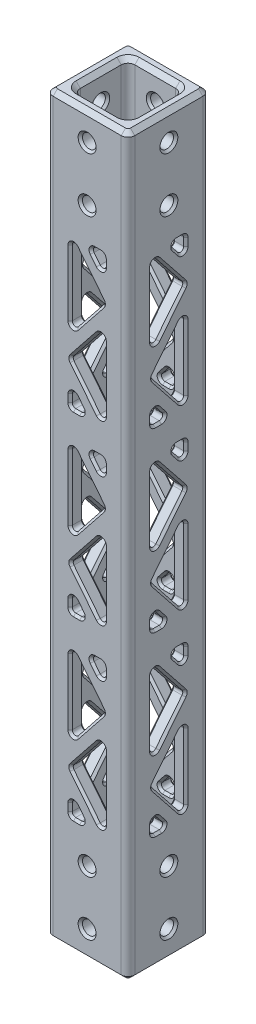
SolidWorks part; units mm, degrees
note: '?' marks a value the reader was unsure of.
ref_plane "Front Plane" through (0, 0, 0) normal (0, 0, 1) x (1, 0, 0)
ref_plane "Top Plane" through (0, 0, 0) normal (0, 1, 0) x (1, 0, 0)
ref_plane "Right Plane" through (0, 0, 0) normal (1, 0, 0) x (0, 0, -1)
sketch "Sketch1" plane through (0, 0, 0) normal (0, 1, 0) x (1, 0, 0)
  line L1 (-9.525, -9.525) -> (9.525, -9.525)
  line L2 (-9.525, -9.525) -> (-9.525, 9.525)
  line L3 (-9.525, 9.525) -> (9.525, 9.525)
  line L4 (9.525, -9.525) -> (9.525, 9.525)
  line L5 (-9.525, -9.525) -> (9.525, 9.525) construction
  line L6 (-9.525, 9.525) -> (9.525, -9.525) construction
  line L7 (-6.35, -6.35) -> (6.35, -6.35)
  line L8 (-6.35, -6.35) -> (-6.35, 6.35)
  line L9 (-6.35, 6.35) -> (6.35, 6.35)
  line L10 (6.35, -6.35) -> (6.35, 6.35)
  line L11 (-6.35, -6.35) -> (6.35, 6.35) construction
  line L12 (-6.35, 6.35) -> (6.35, -6.35) construction
  point P0 (0, 0)
  point P6 (0, 0)
  dimension "D1" = 19.05
  dimension "D2" = 19.05
  dimension "D3" = 12.7
extrude "Boss-Extrude1" add sketch "Sketch1" along normal mid plane 171.45 contours L3 L4 L1 L2
hole_wizard "1/8 (0.125) Diameter Hole1" positions "Sketch8" profile "Sketch9" hole size "1/8" standard "ANSI Inch" end condition through all
sketch "Sketch8" plane through (-9.525, 0, 0) normal (-1, 0, 0) x (0, 0, 1)
  line L4 (-9.525, 85.725) -> (9.525, 85.725) construction
  line L5 (0, 79.375) -> (0, 85.725) construction
  point P0 (0, 79.375)
  point P2 (0, 66.675)
  dimension "D1" = 12.7
  dimension "D2" = 6.35
sketch "Sketch9" plane through (-9.525, 79.375, 0) normal (0, 1, 0) x (0, 0, 1)
  line L0 (0, 0) -> (0, 19.05)
  line L1 (0, 19.05) -> (1.5875, 19.05)
  line L2 (1.5875, 19.05) -> (1.5875, 0)
  line L5 (1.5875, 0) -> (0, 0)
  line L11 (0, -6.35) -> (0, 107.95) construction
  dimension "Thru Hole Dia." = 3.175
  dimension "Thru Hole Depth" = 19.05
hole_wizard "1/8 (0.125) Diameter Hole2" positions "Sketch10" profile "Sketch11" hole size "1/8" standard "ANSI Inch" end condition through all
sketch "Sketch10" plane through (-9.525, 0, 0) normal (-1, 0, 0) x (0, 0, 1)
  line L0 (0, -85.725) -> (0, -79.375) construction
  line L1 (-9.525, -85.725) -> (9.525, -85.725) construction
  point P0 (0, -66.675)
  point P2 (0, -79.375)
  dimension "D1" = 12.7
  dimension "D2" = 6.35
sketch "Sketch11" plane through (-9.525, -66.675, 0) normal (0, 1, 0) x (0, 0, 1)
  line L0 (0, 0) -> (0, 19.05)
  line L1 (0, 19.05) -> (1.5875, 19.05)
  line L2 (1.5875, 19.05) -> (1.5875, 0)
  line L5 (1.5875, 0) -> (0, 0)
  line L11 (0, -6.35) -> (0, 107.95) construction
  dimension "Thru Hole Dia." = 3.175
  dimension "Thru Hole Depth" = 19.05
hole_wizard "1/8 (0.125) Diameter Hole3" positions "Sketch15" profile "Sketch16" hole size "1/8" standard "ANSI Inch" end condition through all
sketch "Sketch15" plane through (0, 0, 9.525) normal (0, 0, 1) x (1, 0, 0)
  line L0 (0, -85.725) -> (0, -79.375) construction
  line L1 (-9.525, -85.725) -> (9.525, -85.725) construction
  line L2 (0, -79.375) -> (0, -66.675) construction
  line L4 (0, 66.675) -> (0, 79.375) construction
  line L5 (0, 79.375) -> (0, 85.725) construction
  line L6 (-9.525, 85.725) -> (9.525, 85.725) construction
  point P0 (0, 79.375)
  point P2 (0, 66.675)
  point P4 (0, -66.675)
  point P6 (0, -79.375)
  dimension "D1" = 6.35
  dimension "D2" = 12.7
sketch "Sketch16" plane through (0, 79.375, 9.525) normal (1, 0, 0) x (0, -1, 0)
  line L0 (0, 0) -> (0, 19.05)
  line L1 (0, 19.05) -> (1.5875, 19.05)
  line L2 (1.5875, 19.05) -> (1.5875, 0)
  line L5 (1.5875, 0) -> (0, 0)
  line L11 (0, -6.35) -> (0, 107.95) construction
  dimension "Thru Hole Dia." = 3.175
  dimension "Thru Hole Depth" = 19.05
sketch "Sketch14" plane through (0, 0, 0) normal (1, 0, 0) x (0, 0, -1)
  line L0 (-3.9688, 58.7375) -> (3.9688, 58.7375) construction
  line L3 (3.9688, 58.7375) -> (3.9688, -58.7375) construction
  line L6 (3.9688, -58.7375) -> (-3.9688, -58.7375) construction
  line L9 (-3.9688, -58.7375) -> (-3.9688, 58.7375) construction
  line L10 (0, 58.7375) -> (0, 65.0875) construction
  line L11 (0, -65.0875) -> (0, -58.7375) construction
  line L12 (-3.9688, 23.8125) -> (3.9688, 23.8125) construction
  line L13 (-3.9688, 17.4625) -> (3.9688, 17.4625) construction
  line L14 (-3.9688, -17.4625) -> (3.9688, -17.4625) construction
  line L15 (-3.9688, -23.8125) -> (3.9688, -23.8125) construction
  line L16 (0, -58.7375) -> (0, -23.8125) construction
  line L17 (0, -23.8125) -> (0, -17.4625) construction
  line L18 (0, -17.4625) -> (0, 17.4625) construction
  line L19 (0, 17.4625) -> (0, 23.8125) construction
  line L20 (0, 23.8125) -> (0, 58.7375) construction
  line L21 (-3.9688, 58.7375) -> (-0.0935, 58.7375)
  line L22 (-0.0935, 58.7375) -> (-3.9688, 53.8821)
  line L23 (-3.9688, 53.8821) -> (-3.9688, 58.7375)
  line L24 (3.9688, 58.7375) -> (-3.9688, 48.7924)
  line L25 (-3.9688, 48.7924) -> (3.9688, 38.8473)
  line L26 (3.9688, 38.8473) -> (3.9688, 58.7375)
  line L27 (-3.9688, 23.8125) -> (3.9688, 33.7576)
  line L28 (3.9688, 33.7576) -> (-3.9688, 43.7027)
  line L29 (-3.9688, 43.7027) -> (-3.9688, 23.8125)
  line L30 (0, 53.765) -> (-2.4815, 55.7455) construction
  line L31 (0, 43.8199) -> (-2.4815, 41.8393) construction
  line L32 (0.0935, 23.8125) -> (3.9688, 23.8125)
  line L33 (3.9688, 23.8125) -> (3.9688, 28.6679)
  line L34 (3.9688, 28.6679) -> (0.0935, 23.8125)
  line L35 (0, 28.785) -> (2.4815, 26.8045) construction
  line L36 (-3.9688, 17.4625) -> (-0.0935, 17.4625)
  line L37 (-0.0935, 17.4625) -> (-3.9688, 12.6071)
  line L38 (-3.9688, 12.6071) -> (-3.9688, 17.4625)
  line L39 (3.9688, 17.4625) -> (-3.9688, 7.5174)
  line L40 (-3.9688, 7.5174) -> (3.9688, -2.4277)
  line L41 (3.9688, -2.4277) -> (3.9688, 17.4625)
  line L42 (0, 12.49) -> (-2.4815, 14.4705) construction
  line L43 (-3.9688, -17.4625) -> (3.9688, -7.5174)
  line L44 (3.9688, -7.5174) -> (-3.9688, 2.4277)
  line L45 (-3.9688, 2.4277) -> (-3.9688, -17.4625)
  line L46 (0, -2.5449) -> (2.4815, -0.5643) construction
  line L47 (0.0935, -17.4625) -> (3.9688, -17.4625)
  line L48 (3.9688, -17.4625) -> (3.9688, -12.6071)
  line L49 (3.9688, -12.6071) -> (0.0935, -17.4625)
  line L50 (2.0311, -15.0348) -> (-0.4504, -13.0542) construction
  line L51 (-3.9688, -23.8125) -> (-0.0935, -23.8125)
  line L52 (-0.0935, -23.8125) -> (-3.9688, -28.6679)
  line L53 (-3.9688, -28.6679) -> (-3.9688, -23.8125)
  line L54 (3.9688, -23.8125) -> (-3.9688, -33.7576)
  line L55 (-3.9688, -33.7576) -> (3.9688, -43.7027)
  line L56 (3.9688, -43.7027) -> (3.9688, -23.8125)
  line L57 (3.9688, -58.7375) -> (0.0935, -58.7375)
  line L58 (0.0935, -58.7375) -> (3.9688, -53.8821)
  line L59 (3.9688, -53.8821) -> (3.9688, -58.7375)
  line L60 (-3.9688, -58.7375) -> (3.9688, -48.7924)
  line L61 (3.9688, -48.7924) -> (-3.9688, -38.8473)
  line L62 (-3.9688, -38.8473) -> (-3.9688, -58.7375)
  line L63 (0, -28.785) -> (-2.4815, -26.8045) construction
  line L64 (0, -38.7301) -> (-2.4815, -40.7107) construction
  line L65 (2.0311, -56.3098) -> (-0.4504, -54.3292) construction
  circle A8 centre (0, 66.675) radius 1.5875 construction
  circle A9 centre (0, -66.675) radius 1.5875 construction
  dimension "D3" = 3.175
  dimension "D2" = 6.35
  dimension "D1" = 7.9375
extrude "Cut-Extrude1" cut sketch "Sketch14" against normal up to next
ref_axis "Axis1" through (0, -87.3125, 0) along (0, 1, 0)?
pattern_circular "CirPattern1" count 4 over 360 about axis through (0, 0, 0) along (0, 1, 0) of "Cut-Extrude1"
fillet "Fillet1" radius 1.5875 8 edges at (9.525, 0, -9.525) (9.525, 0, 9.525) (-9.525, 0, -9.525) (-9.525, 0, 9.525) (6.35, 0, -6.35) (6.35, 0, 6.35) (-6.35, 0, 6.35) (-6.35, 0, -6.35)
fillet "Fillet2" radius 0.7937 71 edges at (-3.9688, 7.5174, -7.9375) (3.9687, -2.4277, -7.9375) (0.0935, 23.8125, -7.9375) (3.9687, 23.8125, -7.9375) (3.9687, 33.7576, -7.9375) (-3.9688, 43.7027, -7.9375) (-0.0935, 17.4625, -7.9375) (-3.9688, -58.7375, -7.9375) (3.9687, -48.7924, -7.9375) (-3.9688, -38.8473, -7.9375) (3.9687, -12.6071, -7.9375) (3.9687, -53.8821, -7.9375) (0.0935, -58.7375, -7.9375) (3.9687, -58.7375, -7.9375) (3.9687, 38.8473, -7.9375) (-3.9688, 53.8821, -7.9375) (-3.9688, 58.7375, -7.9375) (7.9375, -23.8125, 3.9687) (7.9375, -43.7027, 3.9688) (7.9375, -23.8125, -0.0935) (7.9375, -23.8125, -3.9688) (7.9375, 17.4625, 3.9688) (7.9375, 7.5174, -3.9687) (7.9375, 23.8125, 0.0935) (7.9375, 23.8125, -3.9688) (7.9375, 12.6071, -3.9688) (7.9375, 17.4625, -0.0935) (7.9375, 17.4625, -3.9688) (7.9375, -58.7375, -3.9687) (7.9375, -48.7924, 3.9688) (7.9375, -38.8473, -3.9688) (7.9375, -12.6071, 3.9688) (7.9375, -53.8821, 3.9687) (7.9375, -58.7375, 0.0935) (7.9375, 58.7375, 3.9688) (7.9375, 48.7924, -3.9687) (7.9375, 53.8821, -3.9688) (7.9375, 58.7375, -0.0935) (-3.9687, -23.8125, 7.9375) (3.9688, -33.7576, 7.9375) (3.9688, -28.6679, 7.9375) (0.0935, -23.8125, 7.9375) (3.9688, 2.4277, 7.9375) (-3.9687, 17.4625, 7.9375) (3.9688, 7.5174, 7.9375) (-3.9687, -2.4277, 7.9375) (-3.9687, 28.6679, 7.9375) (-3.9687, 33.7576, 7.9375) (3.9688, -38.8473, 7.9375) (-3.9687, -17.4625, 7.9375) (-3.9687, -12.6071, 7.9375) (-0.0935, -58.7375, 7.9375) (0.0935, 58.7375, 7.9375) (-7.9375, -53.8821, -3.9688) (-7.9375, -58.7375, 3.9687) (-7.9375, -33.7576, 3.9688) (-7.9375, -28.6679, 3.9688) (-7.9375, -23.8125, 0.0935) (-7.9375, -12.6071, -3.9688) (-7.9375, 7.5174, 3.9688) (-7.9375, -2.4277, -3.9688) (-7.9375, 17.4625, 0.0935) (-7.9375, 17.4625, 3.9688) (-7.9375, 23.8125, -0.0935) (-7.9375, 28.6679, -3.9688) (-7.9375, 33.7576, -3.9688) (-7.9375, 43.7027, 3.9688) (-7.9375, 48.7924, 3.9688) (-7.9375, 38.8473, -3.9688) (-7.9375, 58.7375, 0.0935) (-7.9375, 58.7375, 3.9688)
chamfer "Chamfer2" distance 1.016 angle 45 32 edges at (5.885, 85.725, -5.885) (0, 85.725, -6.35) (-5.885, 85.725, -5.885) (-6.35, 85.725, 0) (-5.885, 85.725, 5.885) (0, 85.725, 6.35) (5.885, 85.725, 5.885) (6.35, 85.725, 0) (9.06, 85.725, 9.06) (0, 85.725, 9.525) (-9.06, 85.725, 9.06) (-9.525, 85.725, 0) (-9.06, 85.725, -9.06) (0, 85.725, -9.525) (9.06, 85.725, -9.06) (9.525, 85.725, 0) (-5.885, -85.725, -5.885) (0, -85.725, -6.35) (5.885, -85.725, -5.885) (6.35, -85.725, 0) (5.885, -85.725, 5.885) (0, -85.725, 6.35) (-5.885, -85.725, 5.885) (-6.35, -85.725, 0) (-9.06, -85.725, -9.06) (-9.525, -85.725, 0) (-9.06, -85.725, 9.06) (0, -85.725, 9.525) (9.06, -85.725, 9.06) (9.525, -85.725, 0) (9.06, -85.725, -9.06) (0, -85.725, -9.525)
chamfer "Chamfer1" distance 0.508 angle 45 608 edges at (-3.4373, 25.3303, -6.35) (-3.4373, 25.3303, -9.525) (3.7469, 33.7576, -6.35) (3.7469, 33.7576, -9.525) (-3.4373, 42.1849, -6.35) (-3.4373, 42.1849, -9.525) (-3.4373, 14.1249, -6.35) (-3.4373, 14.1249, -9.525) (-1.0274, 17.013, -6.35) (-1.0274, 17.013, -9.525) (-3.7363, 17.23, -6.35) (-3.7363, 17.23, -9.525) (-3.4373, -57.2197, -6.35) (-3.4373, -57.2197, -9.525) (3.7469, -48.7924, -6.35) (3.7469, -48.7924, -9.525) (-3.4373, -40.3651, -6.35) (-3.4373, -40.3651, -9.525) (1.0274, -17.013, -6.35) (1.0274, -17.013, -9.525) (3.7363, -17.23, -6.35) (3.7363, -17.23, -9.525) (3.4373, -14.1249, -6.35) (3.4373, -14.1249, -9.525) (3.4373, -55.3999, -6.35) (3.4373, -55.3999, -9.525) (1.0274, -58.288, -6.35) (1.0274, -58.288, -9.525) (3.7363, -58.505, -6.35) (3.7363, -58.505, -9.525) (3.4373, 57.2197, -6.35) (3.4373, 57.2197, -9.525) (-3.7469, 48.7924, -6.35) (-3.7469, 48.7924, -9.525) (3.4373, 40.3651, -6.35) (3.4373, 40.3651, -9.525) (-3.4373, 55.3999, -6.35) (-3.4373, 55.3999, -9.525) (-1.0274, 58.288, -6.35) (-1.0274, 58.288, -9.525) (-3.7363, 58.505, -6.35) (-3.7363, 58.505, -9.525) (6.35, -25.3303, 3.4373) (9.525, -25.3303, 3.4373) (6.35, -33.7576, -3.7469) (9.525, -33.7576, -3.7469) (6.35, -42.1849, 3.4373) (9.525, -42.1849, 3.4373) (6.35, -27.1501, -3.4373) (9.525, -27.1501, -3.4373) (6.35, -24.262, -1.0274) (9.525, -24.262, -1.0274) (6.35, -24.045, -3.7363) (9.525, -24.045, -3.7363) (6.35, -15.9447, -3.4373) (9.525, -15.9447, -3.4373) (6.35, -7.5174, 3.7469) (9.525, -7.5174, 3.7469) (6.35, 0.9099, -3.4373) (9.525, 0.9099, -3.4373) (6.35, 15.9447, 3.4373) (9.525, 15.9447, 3.4373) (6.35, 7.5174, -3.7469) (9.525, 7.5174, -3.7469) (6.35, -0.9099, 3.4373) (9.525, -0.9099, 3.4373) (6.35, 27.1501, 3.4373) (9.525, 27.1501, 3.4373) (6.35, 24.262, 1.0274) (9.525, 24.262, 1.0274) (6.35, 24.045, 3.7363) (9.525, 24.045, 3.7363) (6.35, 25.3303, -3.4373) (9.525, 25.3303, -3.4373) (6.35, 33.7576, 3.7469) (9.525, 33.7576, 3.7469) (6.35, 42.1849, -3.4373) (9.525, 42.1849, -3.4373) (6.35, 14.1249, -3.4373) (9.525, 14.1249, -3.4373) (6.35, 17.013, -1.0274) (9.525, 17.013, -1.0274) (6.35, 17.23, -3.7363) (9.525, 17.23, -3.7363) (6.35, -57.2197, -3.4373) (9.525, -57.2197, -3.4373) (6.35, -48.7924, 3.7469) (9.525, -48.7924, 3.7469) (6.35, -40.3651, -3.4373) (9.525, -40.3651, -3.4373) (6.35, -17.013, 1.0274) (9.525, -17.013, 1.0274) (6.35, -17.23, 3.7363) (9.525, -17.23, 3.7363) (6.35, -14.1249, 3.4373) (9.525, -14.1249, 3.4373) (6.35, -55.3999, 3.4373) (9.525, -55.3999, 3.4373) (6.35, -58.288, 1.0274) (9.525, -58.288, 1.0274) (6.35, -58.505, 3.7363) (9.525, -58.505, 3.7363) (6.35, 57.2197, 3.4373) (9.525, 57.2197, 3.4373) (6.35, 48.7924, -3.7469) (9.525, 48.7924, -3.7469) (6.35, 40.3651, 3.4373) (9.525, 40.3651, 3.4373) (6.35, 55.3999, -3.4373) (9.525, 55.3999, -3.4373) (6.35, 58.288, -1.0274) (9.525, 58.288, -1.0274) (-3.4373, -25.3303, 6.35) (-3.4373, -25.3303, 9.525) (3.7469, -33.7576, 6.35) (3.7469, -33.7576, 9.525) (-3.4373, -42.1849, 6.35) (-3.4373, -42.1849, 9.525) (3.4373, -27.1501, 6.35) (3.4373, -27.1501, 9.525) (1.0274, -24.262, 6.35) (1.0274, -24.262, 9.525) (3.7363, -24.045, 6.35) (3.7363, -24.045, 9.525) (3.4373, -15.9447, 6.35) (3.4373, -15.9447, 9.525) (-3.7469, -7.5174, 6.35) (-3.7469, -7.5174, 9.525) (3.4373, 0.9099, 6.35) (3.4373, 0.9099, 9.525) (-3.4373, 15.9447, 6.35) (-3.4373, 15.9447, 9.525) (3.7469, 7.5174, 6.35) (3.7469, 7.5174, 9.525) (-3.4373, -0.9099, 6.35) (-3.4373, -0.9099, 9.525) (-3.4373, 27.1501, 6.35) (-3.4373, 27.1501, 9.525) (-1.0274, 24.262, 6.35) (-1.0274, 24.262, 9.525) (-3.7363, 24.045, 6.35) (-3.7363, 24.045, 9.525) (3.4373, 25.3303, 6.35) (3.4373, 25.3303, 9.525) (-3.7469, 33.7576, 6.35) (-3.7469, 33.7576, 9.525) (3.4373, 42.1849, 6.35) (3.4373, 42.1849, 9.525) (3.4373, 14.1249, 6.35) (3.4373, 14.1249, 9.525) (1.0274, 17.013, 6.35) (1.0274, 17.013, 9.525) (3.7363, 17.23, 6.35) (3.7363, 17.23, 9.525) (3.4373, -57.2197, 6.35) (3.4373, -57.2197, 9.525) (-3.7469, -48.7924, 6.35) (-3.7469, -48.7924, 9.525) (3.4373, -40.3651, 6.35) (3.4373, -40.3651, 9.525) (-1.0274, -17.013, 6.35) (-1.0274, -17.013, 9.525) (-3.7363, -17.23, 6.35) (-3.7363, -17.23, 9.525) (-3.4373, -14.1249, 6.35) (-3.4373, -14.1249, 9.525) (-3.4373, -55.3999, 6.35) (-3.4373, -55.3999, 9.525) (-1.0274, -58.288, 6.35) (-1.0274, -58.288, 9.525) (-3.7363, -58.505, 6.35) (-3.7363, -58.505, 9.525) (-3.4373, 57.2197, 6.35) (-3.4373, 57.2197, 9.525) (3.7469, 48.7924, 6.35) (3.7469, 48.7924, 9.525) (-3.4373, 40.3651, 6.35) (-3.4373, 40.3651, 9.525) (3.4373, 55.3999, 6.35) (3.4373, 55.3999, 9.525) (1.0274, 58.288, 6.35) (1.0274, 58.288, 9.525) (3.7363, 58.505, 6.35) (3.7363, 58.505, 9.525) (6.35, 58.505, -3.7363) (9.525, 58.505, -3.7363) (6.35, 66.675, 1.5875) (-6.35, 66.675, -1.5875) (-9.525, 66.675, 1.5875) (9.525, 66.675, 1.5875) (6.35, 79.375, 1.5875) (-6.35, 79.375, -1.5875) (-9.525, 79.375, 1.5875) (9.525, 79.375, 1.5875) (6.35, -79.375, 1.5875) (-6.35, -79.375, -1.5875) (-9.525, -79.375, 1.5875) (9.525, -79.375, 1.5875) (6.35, -66.675, 1.5875) (-6.35, -66.675, -1.5875) (-9.525, -66.675, 1.5875) (9.525, -66.675, 1.5875) (-9.525, -58.7375, -2.4588) (-6.35, -58.7375, -2.4588) (-9.525, -56.5513, -1.8384) (-6.35, -56.5513, -1.8384) (-9.525, -57.0464, -3.9688) (-6.35, -57.0464, -3.9688) (-9.525, -44.4582, -0.5095) (-6.35, -44.4582, -0.5095) (-9.525, -53.1266, -0.5095) (-6.35, -53.1266, -0.5095) (-9.525, -48.7924, 3.9688) (-6.35, -48.7924, 3.9688) (-9.525, -38.0918, 0.5095) (-6.35, -38.0918, 0.5095) (-9.525, -29.4234, 0.5095) (-6.35, -29.4234, 0.5095) (-9.525, -33.7576, -3.9688) (-6.35, -33.7576, -3.9688) (-9.525, -25.9987, 1.8384) (-6.35, -25.9987, 1.8384) (-9.525, -25.5036, 3.9688) (-6.35, -25.5036, 3.9688) (-9.525, -23.8125, 2.4588) (-6.35, -23.8125, 2.4588) (-9.525, -15.7714, -3.9688) (-6.35, -15.7714, -3.9688) (-9.525, -17.4625, -2.4588) (-6.35, -17.4625, -2.4588) (-9.525, -15.2763, -1.8384) (-6.35, -15.2763, -1.8384) (-9.525, -11.8516, -0.5095) (-6.35, -11.8516, -0.5095) (-9.525, -7.5174, 3.9688) (-6.35, -7.5174, 3.9688) (-9.525, -3.1832, -0.5095) (-6.35, -3.1832, -0.5095) (-9.525, 3.1832, 0.5095) (-6.35, 3.1832, 0.5095) (-9.525, 11.8516, 0.5095) (-6.35, 11.8516, 0.5095) (-9.525, 7.5174, -3.9688) (-6.35, 7.5174, -3.9688) (-9.525, 17.4625, 2.4588) (-6.35, 17.4625, 2.4588) (-9.525, 15.2763, 1.8384) (-6.35, 15.2763, 1.8384) (-9.525, 15.7714, 3.9688) (-6.35, 15.7714, 3.9688) (-9.525, 23.8125, -2.4588) (-6.35, 23.8125, -2.4588) (-9.525, 25.9987, -1.8384) (-6.35, 25.9987, -1.8384) (-9.525, 25.5036, -3.9688) (-6.35, 25.5036, -3.9688) (-9.525, 38.0918, -0.5095) (-6.35, 38.0918, -0.5095) (-9.525, 29.4234, -0.5095) (-6.35, 29.4234, -0.5095) (-9.525, 33.7576, 3.9688) (-6.35, 33.7576, 3.9688) (-1.5875, -79.375, 6.35) (-9.525, 44.4582, 0.5095) (1.5875, -79.375, -6.35) (-6.35, 44.4582, 0.5095) (1.5875, -79.375, -9.525) (-9.525, 53.1266, 0.5095) (1.5875, -79.375, 9.525) (-6.35, 53.1266, 0.5095) (-9.525, 48.7924, -3.9688) (-6.35, 48.7924, -3.9688) (-9.525, 58.7375, 2.4588) (-6.35, 58.7375, 2.4588) (-9.525, 56.5513, 1.8384) (-6.35, 56.5513, 1.8384) (-9.525, 57.0464, 3.9688) (-6.35, 57.0464, 3.9688) (-0.5095, -29.4234, -9.525) (-0.5095, -29.4234, -6.35) (3.9687, -33.7576, -9.525) (3.9687, -33.7576, -6.35) (-0.5095, -38.0918, -9.525) (-0.5095, -38.0918, -6.35) (-1.8384, -25.9987, -9.525) (-1.8384, -25.9987, -6.35) (-3.9688, -25.5036, -9.525) (-3.9688, -25.5036, -6.35) (-2.4588, -23.8125, -9.525) (-2.4588, -23.8125, -6.35) (0.5095, -11.8516, -9.525) (0.5095, -11.8516, -6.35) (-3.9688, -7.5174, -9.525) (-3.9688, -7.5174, -6.35) (0.5095, -3.1832, -9.525) (0.5095, -3.1832, -6.35) (-0.5095, 11.8516, -9.525) (-0.5095, 11.8516, -6.35) (3.9687, 7.5174, -9.525) (3.9687, 7.5174, -6.35) (-0.5095, 3.1832, -9.525) (-0.5095, 3.1832, -6.35) (1.8384, 25.9987, -9.525) (1.8384, 25.9987, -6.35) (3.9687, 25.5036, -9.525) (3.9687, 25.5036, -6.35) (2.4588, 23.8125, -9.525) (2.4588, 23.8125, -6.35) (0.5095, 29.4234, -9.525) (0.5095, 29.4234, -6.35) (-3.9688, 33.7576, -9.525) (-3.9688, 33.7576, -6.35) (0.5095, 38.0918, -9.525) (0.5095, 38.0918, -6.35) (-1.8384, 15.2763, -9.525) (-1.8384, 15.2763, -6.35) (-3.9688, 15.7714, -9.525) (-3.9688, 15.7714, -6.35) (-2.4588, 17.4625, -9.525) (-2.4588, 17.4625, -6.35) (0.5095, -53.1266, -9.525) (0.5095, -53.1266, -6.35) (-3.9688, -48.7924, -9.525) (-3.9688, -48.7924, -6.35) (0.5095, -44.4582, -9.525) (0.5095, -44.4582, -6.35) (2.4588, -17.4625, -9.525) (2.4588, -17.4625, -6.35) (1.8384, -15.2763, -9.525) (1.8384, -15.2763, -6.35) (3.9687, -15.7714, -9.525) (3.9687, -15.7714, -6.35) (1.8384, -56.5513, -9.525) (1.8384, -56.5513, -6.35) (3.9687, -57.0464, -9.525) (3.9687, -57.0464, -6.35) (2.4588, -58.7375, -9.525) (2.4588, -58.7375, -6.35) (-0.5095, 53.1266, -9.525) (-0.5095, 53.1266, -6.35) (3.9687, 48.7924, -9.525) (3.9687, 48.7924, -6.35) (-0.5095, 44.4582, -9.525) (-0.5095, 44.4582, -6.35) (1.5875, -66.675, -6.35) (-1.8384, 56.5513, -9.525) (-1.8384, 56.5513, -6.35) (-1.5875, -66.675, 6.35) (1.5875, -66.675, 9.525) (-3.9688, 57.0464, -9.525) (1.5875, -66.675, -9.525) (-3.9688, 57.0464, -6.35) (-2.4588, 58.7375, -9.525) (-2.4588, 58.7375, -6.35) (9.525, -29.4234, -0.5095) (6.35, -29.4234, -0.5095) (9.525, -33.7576, 3.9688) (6.35, -33.7576, 3.9688) (9.525, -38.0918, -0.5095) (6.35, -38.0918, -0.5095) (9.525, -25.9987, -1.8384) (6.35, -25.9987, -1.8384) (9.525, -25.5036, -3.9688) (6.35, -25.5036, -3.9688) (9.525, -23.8125, -2.4588) (6.35, -23.8125, -2.4588) (9.525, -11.8516, 0.5095) (6.35, -11.8516, 0.5095) (9.525, -7.5174, -3.9688) (6.35, -7.5174, -3.9688) (9.525, -3.1832, 0.5095) (6.35, -3.1832, 0.5095) (9.525, 11.8516, -0.5095) (6.35, 11.8516, -0.5095) (9.525, 7.5174, 3.9688) (6.35, 7.5174, 3.9688) (9.525, 3.1832, -0.5095) (6.35, 3.1832, -0.5095) (9.525, 25.9987, 1.8384) (6.35, 25.9987, 1.8384) (9.525, 25.5036, 3.9688) (6.35, 25.5036, 3.9688) (9.525, 23.8125, 2.4588) (6.35, 23.8125, 2.4588) (9.525, 29.4234, 0.5095) (6.35, 29.4234, 0.5095) (9.525, 33.7576, -3.9688) (6.35, 33.7576, -3.9688) (9.525, 38.0918, 0.5095) (6.35, 38.0918, 0.5095) (9.525, 15.2763, -1.8384) (6.35, 15.2763, -1.8384) (9.525, 15.7714, -3.9688) (6.35, 15.7714, -3.9688) (9.525, 17.4625, -2.4588) (6.35, 17.4625, -2.4588) (9.525, -53.1266, 0.5095) (6.35, -53.1266, 0.5095) (9.525, -48.7924, -3.9688) (6.35, -48.7924, -3.9688) (9.525, -44.4582, 0.5095) (6.35, -44.4582, 0.5095) (9.525, -17.4625, 2.4588) (6.35, -17.4625, 2.4588) (9.525, -15.2763, 1.8384) (6.35, -15.2763, 1.8384) (9.525, -15.7714, 3.9688) (6.35, -15.7714, 3.9688) (9.525, -56.5513, 1.8384) (6.35, -56.5513, 1.8384) (9.525, -57.0464, 3.9688) (6.35, -57.0464, 3.9688) (9.525, -58.7375, 2.4588) (6.35, -58.7375, 2.4588) (9.525, 53.1266, -0.5095) (6.35, 53.1266, -0.5095) (9.525, 48.7924, 3.9688) (6.35, 48.7924, 3.9688) (9.525, 44.4582, -0.5095) (6.35, 44.4582, -0.5095) (9.525, 56.5513, -1.8384) (6.35, 56.5513, -1.8384) (9.525, 57.0464, -3.9688) (6.35, 57.0464, -3.9688) (9.525, 58.7375, -2.4588) (6.35, 58.7375, -2.4588) (-1.5875, 66.675, 6.35) (0.5095, -29.4234, 9.525) (0.5095, -29.4234, 6.35) (1.5875, 66.675, -6.35) (1.5875, 66.675, -9.525) (-3.9687, -33.7576, 9.525) (-3.9687, -33.7576, 6.35) (1.5875, 66.675, 9.525) (0.5095, -38.0918, 9.525) (0.5095, -38.0918, 6.35) (1.8384, -25.9987, 9.525) (1.8384, -25.9987, 6.35) (3.9688, -25.5036, 9.525) (3.9688, -25.5036, 6.35) (2.4588, -23.8125, 9.525) (2.4588, -23.8125, 6.35) (-0.5095, -11.8516, 9.525) (-0.5095, -11.8516, 6.35) (3.9688, -7.5174, 9.525) (3.9688, -7.5174, 6.35) (-0.5095, -3.1832, 9.525) (-0.5095, -3.1832, 6.35) (0.5095, 11.8516, 9.525) (0.5095, 11.8516, 6.35) (-3.9687, 7.5174, 9.525) (-3.9687, 7.5174, 6.35) (0.5095, 3.1832, 9.525) (0.5095, 3.1832, 6.35) (-1.8384, 25.9987, 9.525) (-1.8384, 25.9987, 6.35) (-3.9687, 25.5036, 9.525) (-3.9687, 25.5036, 6.35) (-2.4588, 23.8125, 9.525) (-2.4588, 23.8125, 6.35) (-0.5095, 29.4234, 9.525) (-0.5095, 29.4234, 6.35) (3.9688, 33.7576, 9.525) (3.9688, 33.7576, 6.35) (-0.5095, 38.0918, 9.525) (-0.5095, 38.0918, 6.35) (1.8384, 15.2763, 9.525) (1.8384, 15.2763, 6.35) (3.9688, 15.7714, 9.525) (3.9688, 15.7714, 6.35) (2.4588, 17.4625, 9.525) (2.4588, 17.4625, 6.35) (-0.5095, -53.1266, 9.525) (-0.5095, -53.1266, 6.35) (3.9688, -48.7924, 9.525) (3.9688, -48.7924, 6.35) (-0.5095, -44.4582, 9.525) (-0.5095, -44.4582, 6.35) (-2.4588, -17.4625, 9.525) (-2.4588, -17.4625, 6.35) (-1.8384, -15.2763, 9.525) (-1.8384, -15.2763, 6.35) (-3.9687, -15.7714, 9.525) (-3.9687, -15.7714, 6.35) (-1.8384, -56.5513, 9.525) (-1.8384, -56.5513, 6.35) (-3.9687, -57.0464, 9.525) (-3.9687, -57.0464, 6.35) (-2.4588, -58.7375, 9.525) (-2.4588, -58.7375, 6.35) (0.5095, 53.1266, 9.525) (0.5095, 53.1266, 6.35) (-3.9687, 48.7924, 9.525) (-3.9687, 48.7924, 6.35) (0.5095, 44.4582, 9.525) (0.5095, 44.4582, 6.35) (1.8384, 56.5513, 9.525) (1.8384, 56.5513, 6.35) (3.9688, 57.0464, 9.525) (3.9688, 57.0464, 6.35) (2.4588, 58.7375, 9.525) (2.4588, 58.7375, 6.35) (-6.35, -58.288, -1.0274) (-9.525, -58.288, -1.0274) (-6.35, -58.505, -3.7363) (-9.525, -58.505, -3.7363) (-6.35, -55.3999, -3.4373) (-9.525, -55.3999, -3.4373) (-6.35, -48.7924, -3.7469) (-9.525, -48.7924, -3.7469) (-6.35, -57.2197, 3.4373) (-9.525, -57.2197, 3.4373) (-6.35, -40.3651, 3.4373) (-9.525, -40.3651, 3.4373) (-6.35, -33.7576, 3.7469) (-9.525, -33.7576, 3.7469) (-6.35, -42.1849, -3.4373) (-9.525, -42.1849, -3.4373) (-6.35, -25.3303, -3.4373) (-1.5875, 79.375, 6.35) (-9.525, -25.3303, -3.4373) (-6.35, -27.1501, 3.4373) (-9.525, -27.1501, 3.4373) (1.5875, 79.375, -6.35) (-6.35, -24.045, 3.7363) (-9.525, -24.045, 3.7363) (1.5875, 79.375, -9.525) (-6.35, -24.262, 1.0274) (-9.525, -24.262, 1.0274) (-6.35, -17.23, -3.7363) (1.5875, 79.375, 9.525) (-9.525, -17.23, -3.7363) (-6.35, -17.013, -1.0274) (-9.525, -17.013, -1.0274) (-6.35, -14.1249, -3.4373) (-9.525, -14.1249, -3.4373) (-6.35, -15.9447, 3.4373) (-9.525, -15.9447, 3.4373) (-6.35, 0.9099, 3.4373) (-9.525, 0.9099, 3.4373) (-6.35, -7.5174, -3.7469) (-9.525, -7.5174, -3.7469) (-6.35, 7.5174, 3.7469) (-9.525, 7.5174, 3.7469) (-6.35, -0.9099, -3.4373) (-9.525, -0.9099, -3.4373) (-6.35, 15.9447, -3.4373) (-9.525, 15.9447, -3.4373) (-6.35, 17.013, 1.0274) (-9.525, 17.013, 1.0274) (-6.35, 14.1249, 3.4373) (-9.525, 14.1249, 3.4373) (-6.35, 17.23, 3.7363) (-9.525, 17.23, 3.7363) (-6.35, 24.262, -1.0274) (-9.525, 24.262, -1.0274) (-6.35, 24.045, -3.7363) (-9.525, 24.045, -3.7363) (-6.35, 27.1501, -3.4373) (-9.525, 27.1501, -3.4373) (-6.35, 33.7576, -3.7469) (-9.525, 33.7576, -3.7469) (-6.35, 25.3303, 3.4373) (-9.525, 25.3303, 3.4373) (-6.35, 42.1849, 3.4373) (-9.525, 42.1849, 3.4373) (-6.35, 48.7924, 3.7469) (-9.525, 48.7924, 3.7469) (-6.35, 40.3651, -3.4373) (-9.525, 40.3651, -3.4373) (-6.35, 57.2197, -3.4373) (-9.525, 57.2197, -3.4373) (-6.35, 58.288, 1.0274) (-9.525, 58.288, 1.0274) (-6.35, 55.3999, 3.4373) (-9.525, 55.3999, 3.4373) (-6.35, 58.505, 3.7363) (-9.525, 58.505, 3.7363) (3.4373, -25.3303, -6.35) (3.4373, -25.3303, -9.525) (-3.7469, -33.7576, -6.35) (-3.7469, -33.7576, -9.525) (3.4373, -42.1849, -6.35) (3.4373, -42.1849, -9.525) (-3.4373, -27.1501, -6.35) (-3.4373, -27.1501, -9.525) (-1.0274, -24.262, -6.35) (-1.0274, -24.262, -9.525) (-3.7363, -24.045, -6.35) (-3.7363, -24.045, -9.525) (-3.4373, -15.9447, -6.35) (-3.4373, -15.9447, -9.525) (3.7469, -7.5174, -6.35) (3.7469, -7.5174, -9.525) (-3.4373, 0.9099, -6.35) (-3.4373, 0.9099, -9.525) (3.4373, 15.9447, -6.35) (3.4373, 15.9447, -9.525) (-3.7469, 7.5174, -6.35) (-3.7469, 7.5174, -9.525) (3.4373, -0.9099, -6.35) (3.4373, -0.9099, -9.525) (3.4373, 27.1501, -6.35) (3.4373, 27.1501, -9.525) (1.0274, 24.262, -6.35) (1.0274, 24.262, -9.525) (3.7363, 24.045, -6.35) (3.7363, 24.045, -9.525)
equation "\"D2@Sketch1\"=\"D1@Sketch1\""
